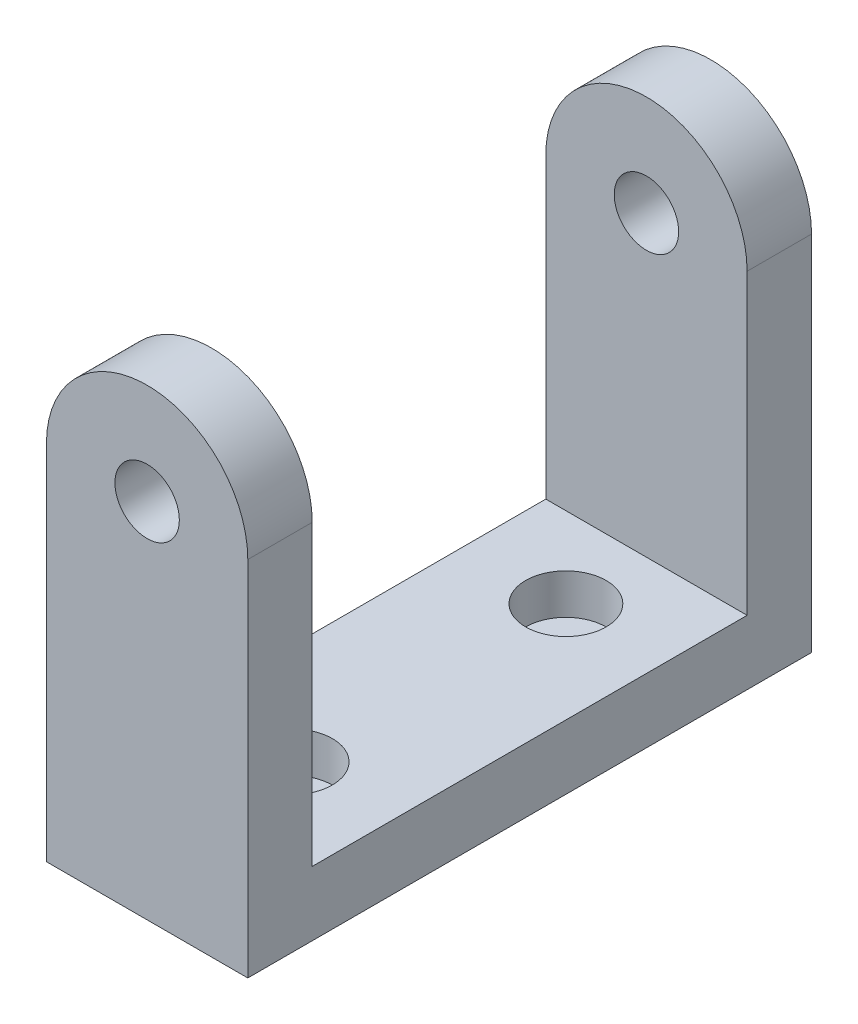
SolidWorks part; units mm, degrees
ref_plane "Ön Düzlem" through (0, 0, 0) normal (0, 0, 1) x (1, 0, 0)
ref_plane "Üst Düzlem" through (0, 0, 0) normal (0, 1, 0) x (1, 0, 0)
ref_plane "Sağ Düzlem" through (0, 0, 0) normal (1, 0, 0) x (0, 0, -1)
sketch "Çizim1" plane through (0, 0, 0) normal (0, 0, 1) x (1, 0, 0)
  line L1 (-28.6932, 40.3256) -> (-3.6932, 40.3256)
  line L2 (-28.6932, 40.3256) -> (-28.6932, -17.1744)
  line L3 (-28.6932, -17.1744) -> (-3.6932, -17.1744)
  line L4 (-3.6932, 40.3256) -> (-3.6932, -17.1744)
  dimension "D1" = 25
  dimension "D2" = 57.5
extrude "Yükseklik-Ekstrüzyon1" add sketch "Çizim1" along normal blind 70
fillet "Radyus1" 2 edges at (-3.6932, 40.3256, 35) (-28.6932, 40.3256, 35) type full round first side face at (-3.6932, 11.5756, 35) second side face at (-28.6932, 11.5756, 35) middle face at (-16.1932, 40.3256, 35)
sketch "Çizim3" plane through (-3.6932, 0, 0) normal (1, 0, 0) x (0, 0, -1)
  line L0 (0, 40.3256) -> (-70, 40.3256) construction
  line L1 (-62, 40.3256) -> (-8, 40.3256)
  line L2 (-62, 40.3256) -> (-62, -9.1744)
  line L3 (-62, -9.1744) -> (-8, -9.1744)
  line L4 (-8, 40.3256) -> (-8, -9.1744)
  line L5 (-70, 40.3256) -> (-70, 27.8256) construction
  line L6 (0, -17.1744) -> (0, 27.8256) construction
  line L7 (-70, -17.1744) -> (0, -17.1744) construction
  dimension "D1" = 8
  dimension "D2" = 8
  dimension "D3" = 8
extrude "Kes-Ekstrüzyon1" cut sketch "Çizim3" against normal through all
sketch "Çizim4" plane through (0, -9.1744, 0) normal (0, 1, 0) x (1, 0, 0)
  line L0 (-3.6932, 0) -> (-28.6932, 0) construction
  circle A0 centre (-16.1932, -18) radius 5
  circle A1 centre (-16.1932, -52) radius 5
  dimension "D3" = 10
  dimension "D4" = 10
  dimension "D1" = 34
  dimension "D2" = 18
extrude "Kes-Ekstrüzyon2" cut sketch "Çizim4" against normal blind 5
sketch "Çizim5" plane through (0, 0, 70) normal (0, 0, 1) x (1, 0, 0)
  circle A0 centre (-16.1932, 27.8256) radius 4
  dimension "D1" = 8
extrude "Kes-Ekstrüzyon3" cut sketch "Çizim5" against normal through all
